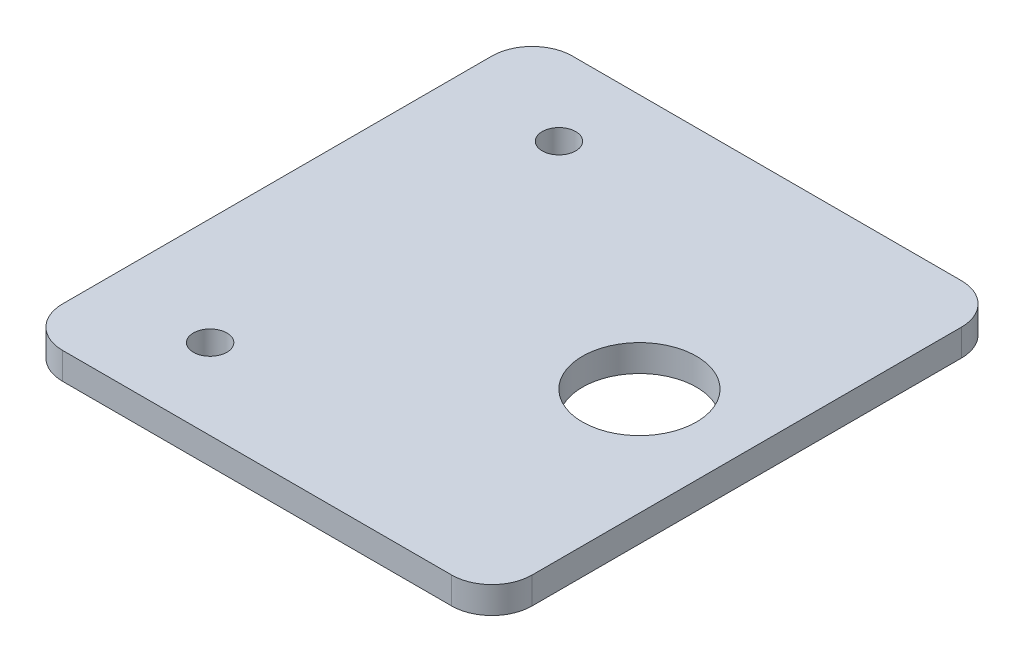
SolidWorks part; units mm, degrees
material "Plain Carbon Steel"
ref_plane "Front Plane" through (0, 0, 0) normal (0, 0, 1) x (1, 0, 0)
ref_plane "Top Plane" through (0, 0, 0) normal (0, 1, 0) x (1, 0, 0)
ref_plane "Right Plane" through (0, 0, 0) normal (1, 0, 0) x (0, 0, -1)
sketch "Sketch1" plane through (0, 0, 0) normal (0, 1, 0) x (1, 0, 0)
  line L0 (-1.5, 19) -> (-1.5, -19) construction
  line L1 (17.5, -19) -> (-17.5, -19)
  line L2 (17.5, -19) -> (17.5, 19)
  line L3 (17.5, 19) -> (-17.5, 19)
  line L4 (-17.5, -19) -> (-17.5, 19)
  line L5 (17.5, -19) -> (-17.5, 19) construction
  line L6 (17.5, 19) -> (-17.5, -19) construction
  line L8 (-9.5, -24.3501) -> (-9.5, 24.7928) construction
  line L9 (0, 0) -> (22.1782, 0) construction
  circle A0 centre (9.5, 0) radius 5 construction
  circle A1 centre (-9.5, 13) radius 1.5 construction
  circle A2 centre (-9.5, -13) radius 1.5 construction
  point P0 (0, 0)
  point P8 (9.5, 0)
  dimension "D4" = 10
  dimension "D6" = 3
  dimension "D1" = 35
  dimension "D2" = 38
  dimension "D3" = 16
  dimension "D5" = 8
  dimension "D7" = 6
  dimension "D8" = 8
base flange "Base-Flange1" sketch "Sketch1" thickness 2 reverse thickness direction no parameters "D1"=1
sketch "Sketch2" plane through (0, 0, 0) normal (0, 1, 0) x (1, 0, 0)
  point P0 (-9.5, -13)
  point P2 (-9.5, 13)
hole_wizard "Tap Drill for M3x0.5 Tap1" positions "Sketch2" profile "Sketch3" hole size "M3x0.5" standard "ANSI Metric" end condition through all
sketch "Sketch3" plane through (-9.5, 0, 13) normal (1, 0, 0) x (0, 0, 1)
  line L0 (0, 0) -> (0, 2)
  line L1 (0, 2) -> (1.25, 2)
  line L2 (1.25, 2) -> (1.25, 0)
  line L5 (1.25, 0) -> (0, 0)
  line L11 (0, -6.35) -> (0, 107.95) construction
  dimension "Thru Hole Dia." = 2.5
  dimension "Thru Hole Depth" = 2
cosmetic thread "Cosmetic Thread1"
cosmetic thread "Cosmetic Thread2"
fillet "Fillet1" radius 3 4 edges at (17.5, -1, -19) (-17.5, -1, -19) (-17.5, -1, 19) (17.5, -1, 19)
sketch "Sketch6" plane through (0, 0, 0) normal (0, 1, 0) x (1, 0, 0)
  circle A0 centre (9.5, 0) radius 5 construction
  circle A1 centre (9.5, 0) radius 5
  point P0 (9.5, 0)
hole_wizard "Tap Drill for M10x1.5 Tap1" positions "Sketch6" profile "Sketch7" hole size "M10x1.5" standard "ANSI Metric"
sketch "Sketch7" plane through (9.5, 0, 0) normal (1, 0, 0) x (0, 0, 1)
  line L0 (0, 0) -> (0, 7.5537)
  line L1 (0, 7.5537) -> (4.25, 5)
  line L2 (4.25, 5) -> (4.25, 0)
  line L5 (4.25, 0) -> (0, 0)
  line L10 (0, 7.5537) -> (-4.25, 5) construction
  line L11 (0, -6.35) -> (0, 107.95) construction
  dimension "Hole Dia." = 8.5
  dimension "Hole Depth" = 5
  dimension "Drill Angle" = 118
cosmetic thread "Cosmetic Thread3"
sketch "Bend-Lines1" [suppressed] plane through (0, 0, 0) normal (0, 1, 0) x (1, 0, 0)
sketch "Bounding-Box1" [suppressed] plane through (0, 0, 0) normal (0, 1, 0) x (1, 0, 0)
sheet metal parameters "Sheet-Metal3" thickness 2 parameters "D1"=1
flat pattern "Flat-Pattern3" [suppressed]
sketch "Bend-Lines2" plane through (0, 0, 0) normal (0, 1, 0) x (1, 0, 0)
sketch3d "Bounding-Box2" [suppressed]
  line L0 (-15, 19, 0) -> (-15, -19, 0) construction
  line L1 (15, 19, 0) -> (15, -19, 0) construction
  line L2 (-15, 19, 0) -> (15, 19, 0) construction
  line L3 (-15, -19, 0) -> (15, -19, 0) construction
sheet metal parameters "Sheet-Metal6" thickness 2 parameters "D1"=1
flat pattern "Flat-Pattern3"
sketch "Bend-Lines2" plane through (0, 0, 0) normal (0, 1, 0) x (1, 0, 0)
sketch3d "Bounding-Box2" [suppressed]
  line L0 (15, 19, 0) -> (15, -19, 0) construction
  line L1 (-15, 19, 0) -> (-15, -19, 0) construction
  line L2 (15, 19, 0) -> (-15, 19, 0) construction
  line L3 (15, -19, 0) -> (-15, -19, 0) construction
sheet metal parameters "Sheet-Metal7" thickness 2 parameters "D1"=1
flat pattern "Flat-Pattern3"
sketch "Bend-Lines2" plane through (0, 0, 0) normal (0, 1, 0) x (1, 0, 0)
sketch3d "Bounding-Box2" [suppressed]
  line L0 (17.5, 19, 0) -> (17.5, -19, 0) construction
  line L1 (-17.5, 19, 0) -> (-17.5, -19, 0) construction
  line L2 (17.5, 19, 0) -> (-17.5, 19, 0) construction
  line L3 (17.5, -19, 0) -> (-17.5, -19, 0) construction
equation "\"D1@Sketch1\"=16+19"
